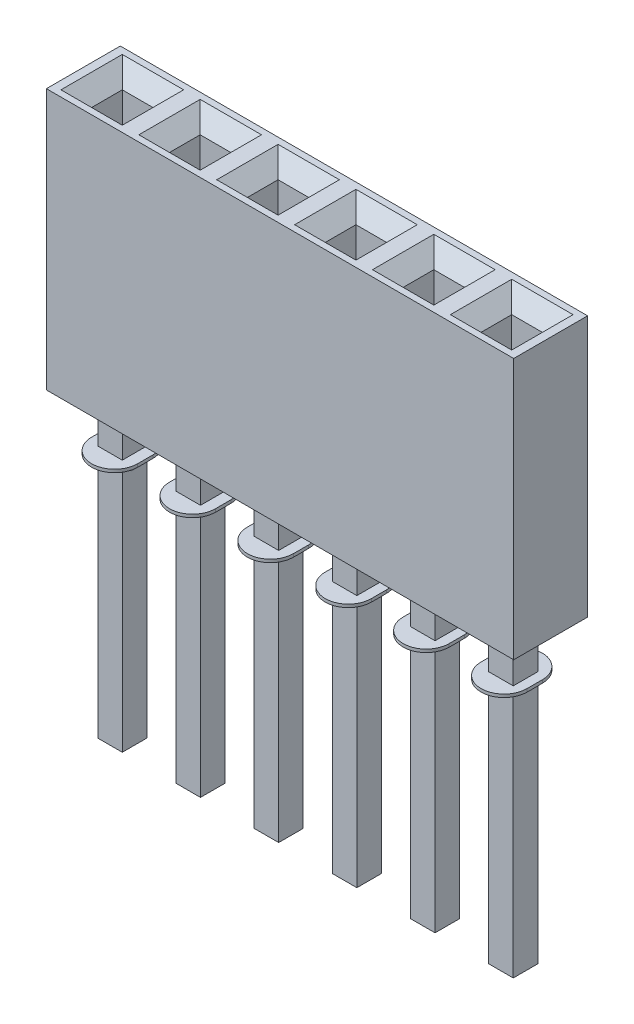
SolidWorks part; units mm, degrees
material "PA Type 6"
ref_plane "Front Plane" through (0, 0, 0) normal (0, 0, 1) x (1, 0, 0)
ref_plane "Top Plane" through (0, 0, 0) normal (0, 1, 0) x (1, 0, 0)
ref_plane "Right Plane" through (0, 0, 0) normal (1, 0, 0) x (0, 0, -1)
ref_plane "Plane1" through (0, -1.65, 0) normal (0, 1, 0) x (1, 0, 0)
sketch "Sketch2" plane through (0, 0, 0) normal (0, 1, 0) x (1, 0, 0)
  line L0 (0, -55) -> (0, 55) construction
  line L1 (-1.27, 1.205) -> (13.97, 1.205)
  line L2 (-1.27, 1.205) -> (-1.27, -1.205)
  line L3 (-1.27, -1.205) -> (13.97, -1.205)
  line L4 (13.97, 1.205) -> (13.97, -1.205)
  line L5 (-55, 0) -> (55, 0) construction
  dimension "D1" = 15.24
  dimension "D2" = 1.27
  dimension "D3" = 2.41
  dimension "D4" = 1.205
extrude "Boss-Extrude1" add sketch "Sketch2" along normal blind 8.51
sketch "Sketch5" plane through (0, 8.51, 0) normal (0, 1, 0) x (1, 0, 0)
  line L0 (-55, 0) -> (55, 0) construction
  line L1 (0.5, 0.5) -> (-0.5, 0.5)
  line L2 (0.5, 0.5) -> (0.5, -0.5)
  line L3 (0.5, -0.5) -> (-0.5, -0.5)
  line L4 (-0.5, 0.5) -> (-0.5, -0.5)
  line L5 (0, -55) -> (0, 55) construction
  dimension "D1" = 0.5
  dimension "D2" = 1
  dimension "D3" = 0.5
extrude "Cut-Extrude1" cut sketch "Sketch5" against normal blind 5
chamfer "Chamfer1" distance 0.5 angle 45 4 edges at (-0.5, 8.51, 0) (0, 8.51, 0.5) (0.5, 8.51, 0) (0, 8.51, -0.5)
pattern_linear "LPattern3" count 6 spacing 2.54 along (1, 0, 0) of "Chamfer1", "Cut-Extrude1"
sketch "Sketch8" plane through (0, 0, 0) normal (0, 1, 0) x (1, 0, 0)
  line L0 (0, -1.3255) -> (0, 1.3255) construction
  line L1 (-0.3, -0.2) -> (0.3, -0.2)
  line L2 (-0.4, -0.1) -> (-0.4, 0.1)
  line L3 (-0.3, 0.2) -> (0.3, 0.2)
  line L4 (0.4, -0.1) -> (0.4, 0.1)
  line L5 (-4.6805, 0) -> (4.6805, 0) construction
  arc A0 (-0.3, -0.2) -> (-0.4, -0.1) centre (-0.3, -0.1) cw
  arc A1 (0.3, -0.2) -> (0.4, -0.1) centre (0.3, -0.1) ccw
  arc A2 (0.3, 0.2) -> (0.4, 0.1) centre (0.3, 0.1) cw
  arc A3 (-0.4, 0.1) -> (-0.3, 0.2) centre (-0.3, 0.1) cw
  point P10 (-0.4, -0.2)
  point P13 (0.4, -0.2)
  point P16 (0.4, 0.2)
  dimension "D5" = 0.1
  dimension "D1" = 0.4
  dimension "D2" = 0.8
  dimension "D3" = 0.4
  dimension "D4" = 0.2
extrude "Boss-Extrude2" add sketch "Sketch8" against normal blind 2
sketch "Sketch10" plane through (0, -1.65, 0) normal (0, 1, 0) x (1, 0, 0)
  line L0 (0, -0.25) -> (0, 0.25) construction
  line L1 (0, -1.3255) -> (0, 1.3255) construction
  line L2 (-0.75, -0.25) -> (-0.75, 0.25)
  line L3 (0.75, -0.25) -> (0.75, 0.25)
  line L4 (-5.7805, 0) -> (5.7805, 0) construction
  arc A0 (-0.75, -0.25) -> (0.75, -0.25) centre (0, -0.25) ccw
  arc A1 (0.75, 0.25) -> (-0.75, 0.25) centre (0, 0.25) ccw
  point P5 (0, 0)
  dimension "D1" = 1.5
  dimension "D2" = 0.5
extrude "Boss-Extrude3" add sketch "Sketch10" along normal blind 0.1
fillet "Fillet2" radius 0.4 6 edges at (-0.3707, -1.65, -0.1707) (-0.3707, -1.65, 0.1707) (0, -1.65, 0.2) (0.3707, -1.65, 0.1707) (0.3707, -1.65, -0.1707) (0, -1.65, -0.2)
pattern_linear "LPattern1" count 6 spacing 2.54 along (1, 0, 0) of "Boss-Extrude2", "Fillet2", "Boss-Extrude3"
ref_axis "Axis1" through (0, -2.5255, 0) along (0, 1, 0)
sketch "Esquisse1" plane through (0, -2, 0) normal (0, -1, 0) x (-1, 0, 0)
  line L0 (-2.95, 0.4) -> (-2.15, 0.4)
  line L1 (-0.4, -0.4) -> (0.4, -0.4)
  line L2 (-0.4, -0.4) -> (-0.4, 0.4)
  line L3 (-0.4, 0.4) -> (0.4, 0.4)
  line L4 (0.4, -0.4) -> (0.4, 0.4)
  line L5 (-0.4, -0.4) -> (0.4, 0.4) construction
  line L6 (-0.4, 0.4) -> (0.4, -0.4) construction
  line L7 (-2.95, -0.4) -> (-2.95, 0.4)
  line L8 (-2.95, -0.4) -> (-2.15, -0.4)
  line L9 (-2.15, -0.4) -> (-2.15, 0.4)
  line L10 (-5.5, 0.4) -> (-4.7, 0.4)
  line L11 (-5.5, -0.4) -> (-5.5, 0.4)
  line L12 (-5.5, -0.4) -> (-4.7, -0.4)
  line L13 (-4.7, -0.4) -> (-4.7, 0.4)
  line L14 (-8.05, 0.4) -> (-7.25, 0.4)
  line L15 (-8.05, -0.4) -> (-8.05, 0.4)
  line L16 (-8.05, -0.4) -> (-7.25, -0.4)
  line L17 (-7.25, -0.4) -> (-7.25, 0.4)
  line L18 (-10.6, 0.4) -> (-9.8, 0.4)
  line L19 (-10.6, -0.4) -> (-10.6, 0.4)
  line L20 (-10.6, -0.4) -> (-9.8, -0.4)
  line L21 (-9.8, -0.4) -> (-9.8, 0.4)
  line L22 (-13.15, 0.4) -> (-12.35, 0.4)
  line L23 (-13.15, -0.4) -> (-13.15, 0.4)
  line L24 (-13.15, -0.4) -> (-12.35, -0.4)
  line L25 (-12.35, -0.4) -> (-12.35, 0.4)
  point P0 (0, 0)
  dimension "D1" = 0.8
  dimension "D2" = 0.8
  dimension "D3" = 6
extrude "Boss.-Extru.1" add sketch "Esquisse1" along normal blind 8 and the other way blind 2.4
chamfer "Chanfrein1" distance 0.2 angle 45 24 edges at (12.75, -10, 0.4) (13.15, -10, 0) (12.75, -10, -0.4) (12.35, -10, 0) (0, -10, 0.4) (0.4, -10, 0) (0, -10, -0.4) (-0.4, -10, 0) (2.55, -10, 0.4) (2.95, -10, 0) (2.55, -10, -0.4) (2.15, -10, 0) (5.1, -10, 0.4) (5.5, -10, 0) (5.1, -10, -0.4) (4.7, -10, 0) (7.65, -10, 0.4) (8.05, -10, 0) (7.65, -10, -0.4) (7.25, -10, 0) (10.2, -10, 0.4) (10.6, -10, 0) (10.2, -10, -0.4) (9.8, -10, 0)
equation "\"D1@Sketch2\"=2.54 *6"
